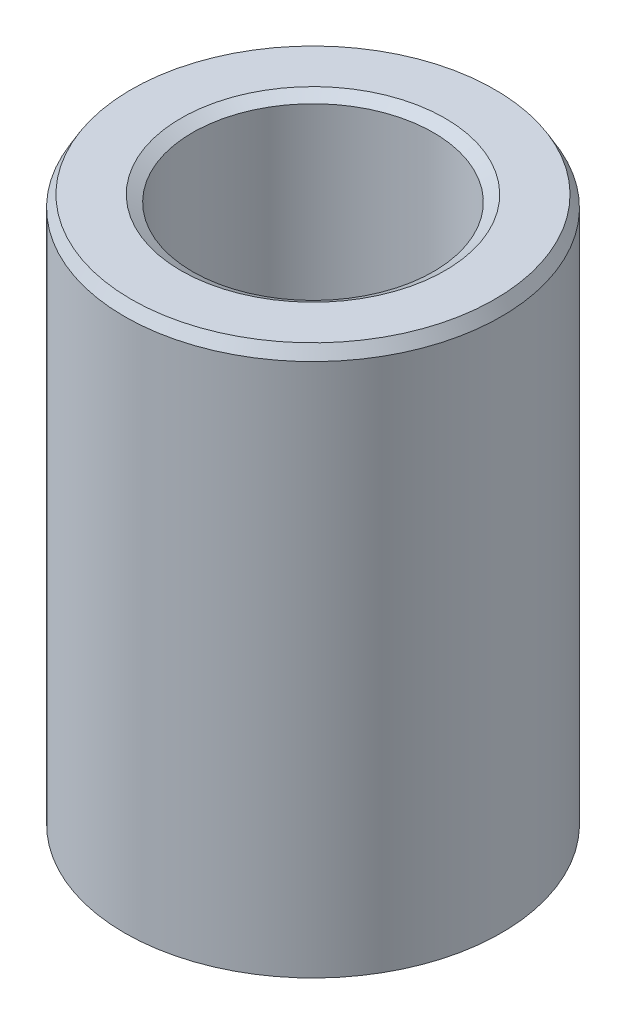
SolidWorks part; units mm, degrees
ref_plane "Front Plane" through (0, 0, 0) normal (0, 0, 1) x (1, 0, 0)
ref_plane "Top Plane" through (0, 0, 0) normal (0, 1, 0) x (1, 0, 0)
ref_plane "Right Plane" through (0, 0, 0) normal (1, 0, 0) x (0, 0, -1)
sketch "Sketch1" plane through (0, 0, 0) normal (0, 1, 0) x (1, 0, 0)
  circle A0 centre (0, 0) radius 42.5
  dimension "SLEEVE_OD" = 85
extrude "Boss-Extrude1" add sketch "Sketch1" along normal blind 124.5114
sketch "Sketch2" plane through (0, 0, 0) normal (0, 1, 0) x (1, 0, 0)
  circle A0 centre (0, 0) radius 27.1735
  dimension "BORE_D" = 54.347
extrude "Cut-Extrude1" cut sketch "Sketch2" along normal through all
chamfer "Chamfer1" distance 2.6094 angle 29.914 4 edges at (0, 124.5114, 27.1735) (0, 0, 27.1735) (0, 0, 42.5) (0, 124.5114, 42.5) first distance on face at (0, 124.5114, 27.1735) first distance on face at (0, 0, 27.1735) first distance on face at (0, 124.5114, 42.5)
